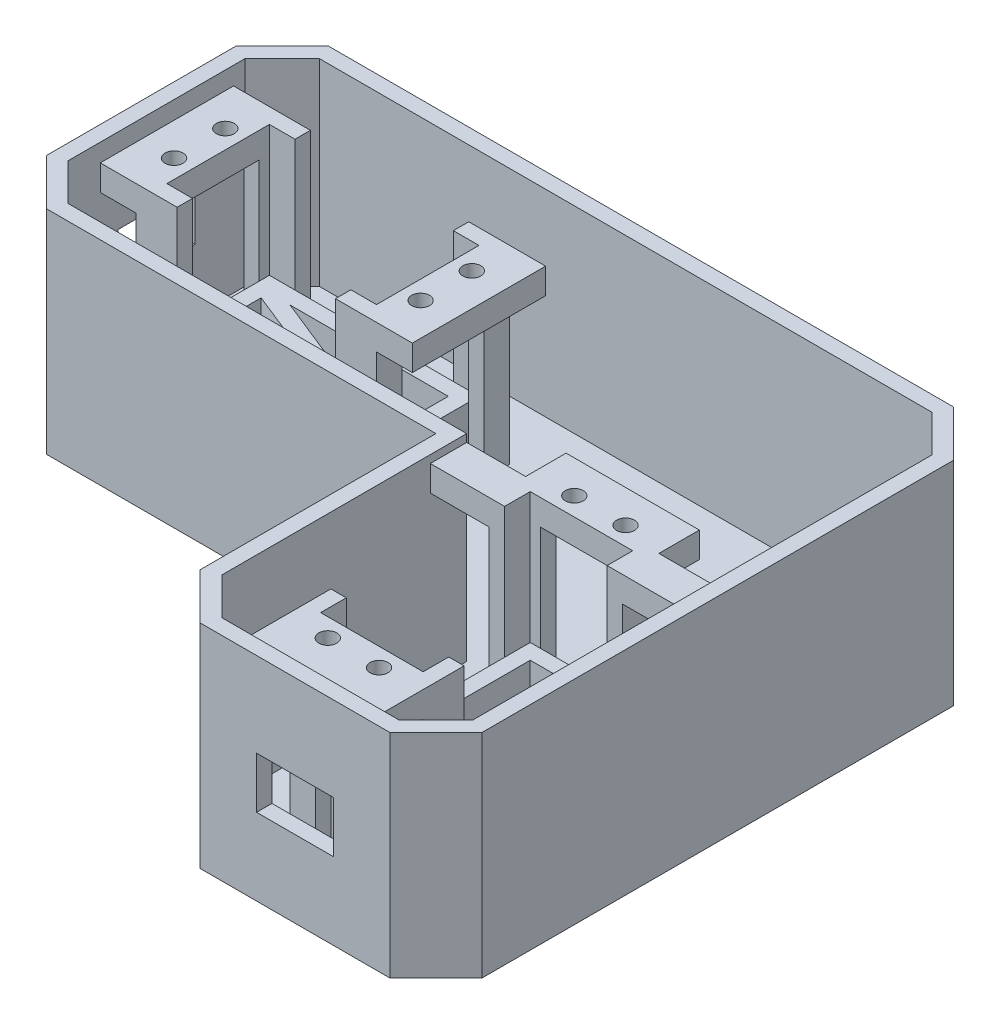
SolidWorks part; units mm, degrees
ref_plane "Front Plane" through (0, 0, 0) normal (0, 0, 1) x (1, 0, 0)
ref_plane "Top Plane" through (0, 0, 0) normal (0, 1, 0) x (1, 0, 0)
ref_plane "Right Plane" through (0, 0, 0) normal (1, 0, 0) x (0, 0, -1)
sketch "Sketch2" plane through (0, 0, 0) normal (0, 1, 0) x (1, 0, 0)
  line L0 (0, 46) -> (9, 55)
  line L1 (9, 0) -> (140, 0)
  line L2 (0, 9) -> (0, 46)
  line L3 (9, 55) -> (131, 55)
  line L4 (140, 0) -> (140, 46)
  line L5 (140, 0) -> (85, 0)
  line L6 (140, 0) -> (140, -46)
  line L7 (131, -55) -> (94, -55)
  line L8 (85, 0) -> (85, -46)
  line L9 (0, 9) -> (9, 0)
  line L10 (94, -55) -> (85, -46)
  line L11 (140, -46) -> (131, -55)
  line L12 (131, 55) -> (140, 46)
  point P0 (0, 0)
  point P1 (140, 55)
  point P2 (0, 55)
  point P5 (85, -55)
  point P6 (140, -55)
  dimension "D1" = 55
  dimension "D2" = 140
  dimension "D3" = 55
  dimension "D4" = 55
extrude "Boss-Extrude1" add sketch "Sketch2" along normal blind 55 contours L12 L3 L0 L2 L9 L1 L4 | L6 L11 L7 L10 L8 L5
shell "Shell1" thickness 3
ref_plane "Plane1" through (0, 41.5, 0) normal (0, 1, 0) x (1, 0, 0)
sketch "Sketch4" plane through (0, 0, 0) normal (0, 0, 1) x (1, 0, 0)
  line L0 (60.5, 41.5) -> (-60.5, 41.5) construction
  line L1 (-7.3258, 41.5) -> (147.3258, 41.5)
  line L2 (-7.3258, 41.5) -> (-7.3258, 64.0976)
  line L3 (-7.3258, 64.0976) -> (147.3258, 64.0976)
  line L4 (147.3258, 41.5) -> (147.3258, 64.0976)
  line L6 (-7.3258, 41.5) -> (147.3258, 41.5)
  line L7 (-7.3258, 41.5) -> (-7.3258, -2.7209)
  line L8 (-7.3258, -2.7209) -> (147.3258, -2.7209)
  line L9 (147.3258, 41.5) -> (147.3258, -2.7209)
extrude "Cut-Extrude1" cut sketch "Sketch4" against normal through all both and the other way through all contours L2 L1 L4 L3
sketch "Sketch5" plane through (0, 41.5, 0) normal (0, 1, 0) x (1, 0, 0)
  line L0 (112.5, -55) -> (112.5, -30) construction
  line L1 (94, -55) -> (131, -55) construction
  line L2 (112.5, -30) -> (112.5, -40) construction
  line L4 (102.5, 0.9) -> (122.5, 0.9)
  line L5 (102.5, 0.9) -> (102.5, -40)
  line L6 (102.5, -40) -> (122.5, -40)
  line L7 (122.5, 0.9) -> (122.5, -40)
  circle A0 centre (112.5, -30) radius 2.5
  point P9 (112.5, -40)
  dimension "D5" = 5
  dimension "D1" = 25
  dimension "D2" = 10
  dimension "D3" = 40.9
  dimension "D4" = 20
sketch "Sketch6" plane through (0, 0, 0) normal (0, -1, 0) x (1, 0, 0)
  line L0 (112.5, 55) -> (112.5, 30) construction
  circle A0 centre (112.5, 30) radius 3.8
  dimension "D1" = 7.6
extrude "Boss-Extrude2" add sketch "Sketch6" along normal blind 6
sketch "Sketch8" plane through (0, 3, 0) normal (0, 1, 0) x (1, 0, 0)
  line L0 (99.5, -35) -> (99.5, -43)
  line L1 (104.5, -43) -> (99.5, -43)
  line L4 (99.5, -4.1) -> (125.5, -4.1)
  line L5 (122.5, 0.9) -> (102.5, 0.9)
  line L6 (102.5, 0.9) -> (102.5, -40)
  line L7 (102.5, -40) -> (122.5, -40)
  line L8 (125.5, 3.9) -> (99.5, 3.9)
  line L9 (99.5, 3.9) -> (99.5, -43)
  line L10 (125.5, -43) -> (125.5, 3.9)
  line L11 (99.5, -43) -> (125.5, -43)
  line L12 (125.5, 3.9) -> (99.5, 3.9)
  line L13 (99.5, 3.9) -> (99.5, -43)
  line L14 (125.5, -43) -> (125.5, 3.9)
  line L15 (99.5, -43) -> (125.5, -43)
  line L16 (122.5, -40) -> (122.5, 0.9)
  line L17 (125.5, -4.1) -> (125.5, -35)
  line L18 (125.5, -35) -> (99.5, -35)
  line L19 (104.5, 3.9) -> (104.5, -43)
  line L20 (104.5, -43) -> (120.5, -43)
  line L21 (120.5, -43) -> (120.5, 3.9)
  line L22 (99.5, -4.1) -> (102.5, -4.1)
  line L23 (102.5, -4.1) -> (102.5, 0.9)
  line L24 (102.5, 0.9) -> (104.5, 0.9)
  line L25 (104.5, 0.9) -> (104.5, 3.9)
  line L26 (120.5, 3.9) -> (120.5, 0.9)
  line L27 (120.5, 0.9) -> (122.5, 0.9)
  line L28 (122.5, -4.1) -> (122.5, 0.9)
  line L29 (122.5, -4.1) -> (125.5, -4.1)
  line L30 (125.5, -35) -> (122.5, -35)
  line L31 (122.5, -35) -> (122.5, -40)
  line L32 (122.5, -40) -> (120.5, -40)
  line L33 (120.5, -40) -> (120.5, -43)
  line L34 (120.5, -43) -> (125.5, -43)
  line L35 (104.5, -43) -> (104.5, -40)
  line L36 (104.5, -40) -> (102.5, -40)
  line L37 (102.5, -40) -> (102.5, -35)
  line L38 (102.5, -35) -> (99.5, -35)
  dimension "D5" = 5
  dimension "D2" = 8
  dimension "D4" = 8
  dimension "D6" = 5
extrude "Boss-Extrude3" add sketch "Sketch8" along normal blind 37 contours L7 L6 L28 L23 L24 L25 | L21 L15 L14 L18 L16 L7 | L16 L14 L12 L5 | L19 L12 L13 L4 L6 L5 region at (101.5, 3, 39.5) region at (101.5, 3, -0.4) region at (123.5, 3, 39.5) region at (123.5, 3, -0.4)
sketch "Sketch9" plane through (0, 40, 0) normal (0, 1, 0) x (1, 0, 0)
  line L3 (99.5, 10.9) -> (125.5, 10.9)
  line L7 (99.5, -50) -> (125.5, -50)
  line L8 (125.5, -43) -> (125.5, -35) construction
  line L11 (99.5, -40) -> (125.5, -40)
  line L13 (99.5, 3.9) -> (99.5, -4.1) construction
  line L16 (125.5, 0.9) -> (99.5, 0.9)
  line L18 (99.5, -40) -> (99.5, -50)
  line L19 (125.5, -50) -> (125.5, -40)
  line L20 (125.5, 0.9) -> (125.5, 10.9)
  line L21 (99.5, 10.9) -> (99.5, 0.9)
  line L22 (99.5, -50) -> (125.5, -40) construction
  line L23 (99.5, 0.9) -> (125.5, 10.9) construction
  dimension "D2" = 10
  dimension "D1" = 10
  dimension "D3" = 26
  dimension "D4" = 26
  dimension "D5" = 40.9
extrude "Boss-Extrude4" add sketch "Sketch9" against normal blind 5
sketch "Sketch10" plane through (0, 40, 0) normal (0, 1, 0) x (1, 0, 0)
  line L0 (112.5, 10.9) -> (112.5, -50) construction
  line L1 (125.5, 10.9) -> (99.5, 10.9) construction
  line L2 (99.5, -50) -> (125.5, -50) construction
  line L3 (107.5, 4.5) -> (117.5, 4.5)
  line L4 (102.5, -19.55) -> (122.5, -19.55) construction
  line L5 (102.5, 0.9) -> (102.5, -40) construction
  line L6 (122.5, 0.9) -> (122.5, -40) construction
  line L7 (102.5, 0.9) -> (122.5, 0.9) construction
  circle A0 centre (107.5, 4.5) radius 1.75
  circle A1 centre (117.5, 4.5) radius 1.75
  circle A2 centre (117.5, -43.6) radius 1.75
  circle A3 centre (107.5, -43.6) radius 1.75
  point P9 (112.5, 4.5)
  dimension "D2" = 10
  dimension "D1" = 3.5
  dimension "D3" = 3.6
extrude "Cut-Extrude3" cut sketch "Sketch10" against normal up to next contours A0 | A1 | A2 | A3 region at (117.5, 40, -6.2005) region at (105.7995, 40, -4.5)
sketch "Sketch11" plane through (0, 40, 0) normal (0, 1, 0) x (1, 0, 0)
  line L0 (129.7574, -52) -> (95.2426, -52) construction
  line L1 (125.5, -52) -> (99.5, -52)
  line L2 (125.5, -52) -> (125.5, -50)
  line L3 (125.5, -50) -> (99.5, -50)
  line L4 (99.5, -52) -> (99.5, -50)
  line L5 (137, -44.7574) -> (137, 44.7574) construction
  line L6 (88, 3) -> (99.5, 3)
  line L7 (88, 3) -> (88, -4.1)
  line L8 (88, -4.1) -> (99.5, -4.1)
  line L9 (99.5, 3) -> (99.5, -4.1)
  line L10 (125.5, -4.1) -> (137, -4.1)
  line L11 (125.5, -4.1) -> (125.5, 3)
  line L12 (125.5, 3) -> (137, 3)
  line L13 (137, -4.1) -> (137, 3)
  dimension "D1" = 26
extrude "Boss-Extrude5" add sketch "Sketch11" against normal blind 5
sketch "Sketch12" plane through (0, 0, 55) normal (0, 0, 1) x (1, 0, 0)
  line L0 (112.5, 0) -> (112.5, 15) construction
  line L1 (131, 0) -> (94, 0) construction
  line L3 (105, 25) -> (120, 25)
  line L4 (105, 25) -> (105, 15)
  line L5 (105, 15) -> (120, 15)
  line L6 (120, 25) -> (120, 15)
  point P8 (112.5, 15)
  dimension "D2" = 10
  dimension "D1" = 15
  dimension "D3" = 15
extrude "Cut-Extrude4" cut sketch "Sketch12" against normal up to next
sketch "Sketch13" plane through (0, 3, 0) normal (0, 1, 0) x (1, 0, 0)
  line L1 (102.5, 0.9) -> (122.5, 0.9)
  line L2 (102.5, 0.9) -> (102.5, -40)
  line L3 (102.5, -40) -> (122.5, -40)
  line L4 (122.5, 0.9) -> (122.5, -40)
extrude "Boss-Extrude6" add sketch "Sketch13" along normal blind 11.5
sketch "Sketch14" plane through (0, 14.5, 0) normal (0, 1, 0) x (1, 0, 0)
  line L0 (112.5, 0.9) -> (112.5, -40) construction
  line L1 (102.5, 0.9) -> (122.5, 0.9) construction
  line L26 (105.5, -2.1) -> (105.5, -4.1)
  line L27 (105.5, -4.1) -> (105.5, -35)
  line L28 (105.5, -35) -> (105.5, -37)
  line L29 (105.5, -37) -> (119.5, -37)
  line L30 (119.5, -37) -> (119.5, -35)
  line L31 (119.5, -35) -> (119.5, -4.1)
  line L32 (119.5, -4.1) -> (119.5, -2.1)
  line L33 (119.5, -2.1) -> (105.5, -2.1)
  line L34 (105.5, -2.1) -> (105.5, -4.1)
  line L35 (105.5, -4.1) -> (105.5, -35)
  line L36 (105.5, -35) -> (105.5, -37)
  line L37 (105.5, -37) -> (119.5, -37)
  line L38 (119.5, -37) -> (119.5, -35)
  line L39 (119.5, -35) -> (119.5, -4.1)
  line L40 (119.5, -4.1) -> (119.5, -2.1)
  line L41 (119.5, -2.1) -> (105.5, -2.1)
  dimension "D1" = 3
extrude "Cut-Extrude5" cut sketch "Sketch14" against normal up to surface (11.5 mm away) up to face at (75.5675, 3, -1.4766)
sketch "Sketch15" plane through (0, 3, 0) normal (0, 1, 0) x (1, 0, 0)
  line L0 (119.5, -2.1) -> (105.5, -37) construction
  line L1 (105.5, -32.9711) -> (117.8838, -2.1)
  line L2 (111.1078, -18.9915) -> (113.8922, -20.1085)
  line L3 (107.1162, -37) -> (119.5, -6.1289)
  line L5 (105.5, -2.1) -> (119.5, -2.1)
  line L6 (105.5, -2.1) -> (105.5, -37)
  line L7 (105.5, -37) -> (119.5, -37)
  line L8 (119.5, -2.1) -> (119.5, -37)
  point P11 (112.5, -19.55)
  point P12 (111.1078, -18.9915)
  point P15 (113.8922, -20.1085)
  line M6 (119.5, -2.1) -> (105.5, -2.1)
  line M7 (105.5, -2.1) -> (105.5, -37)
  line M8 (105.5, -37) -> (119.5, -37)
  line M9 (119.5, -37) -> (119.5, -2.1)
extrude "Boss-Extrude7" add sketch "Sketch15" along normal blind 11.5 contours L0 L1 L2 M6 | L0 L2 L3 M9 | L0 L2 L1 M7 | L2 L0 L3 M8 region at (116.3352, 3, 11.9296) region at (115.252, 3, 10.6861) region at (109.748, 3, 28.4139) region at (108.6648, 3, 27.1704)
sketch "Sketch16" plane through (0, 0, 0) normal (-1, 0, 0) x (0, 0, 1)
  line L0 (-27.5, 0) -> (-27.5, 15) construction
  line L1 (-35, 25) -> (-20, 25)
  line L2 (-35, 25) -> (-35, 15)
  line L3 (-35, 15) -> (-20, 15)
  line L4 (-20, 25) -> (-20, 15)
  line L5 (-9, 0) -> (-46, 0) construction
  point P6 (-27.5, 15)
  point P9 (-27.5, 0)
  dimension "D1" = 15
  dimension "D2" = 10
  dimension "D3" = 15
extrude "Cut-Extrude6" cut sketch "Sketch16" against normal up to next
sketch "Sketch17" plane through (0, 41.5, 0) normal (0, 1, 0) x (1, 0, 0)
  line L0 (0, 27.5) -> (25, 27.5) construction
  line L1 (25, 27.5) -> (15, 27.5) construction
  line L2 (55.9, 37.5) -> (55.9, 17.5)
  line L3 (55.9, 37.5) -> (15, 37.5)
  line L4 (15, 37.5) -> (15, 17.5)
  line L5 (55.9, 17.5) -> (15, 17.5)
  line L6 (0, 46) -> (0, 9) construction
  line L8 (15, 37.5) -> (55.9, 37.5)
  line L9 (15, 37.5) -> (15, 17.5)
  line L10 (15, 17.5) -> (55.9, 17.5)
  line L11 (55.9, 37.5) -> (55.9, 17.5)
  circle A0 centre (25, 27.5) radius 2.5
  point P7 (15, 27.5)
  point P11 (0, 27.5)
  dimension "D1" = 25
  dimension "D2" = 5
  dimension "D3" = 20
  dimension "D4" = 40.9
  dimension "D5" = 10
  dimension "D6" = 30.9
sketch "Sketch18" plane through (0, 3, 0) normal (0, 1, 0) x (1, 0, 0)
  line L4 (55.9, 17.5) -> (55.9, 37.5)
  line L5 (55.9, 37.5) -> (15, 37.5)
  line L6 (15, 37.5) -> (15, 17.5)
  line L7 (15, 17.5) -> (55.9, 17.5)
  line L8 (58.9, 14.5) -> (58.9, 40.5)
  line L9 (12, 14.5) -> (58.9, 14.5)
  line L10 (12, 40.5) -> (12, 14.5)
  line L11 (58.9, 40.5) -> (12, 40.5)
  line L12 (58.9, 14.5) -> (58.9, 40.5)
  line L13 (12, 14.5) -> (58.9, 14.5)
  line L14 (12, 40.5) -> (12, 14.5)
  line L15 (58.9, 40.5) -> (12, 40.5)
  line L16 (12, 35.5) -> (58.9, 35.5)
  line L17 (58.9, 19.5) -> (12, 19.5)
  line L18 (20, 40.5) -> (20, 14.5)
  line L20 (50.9, 40.5) -> (50.9, 14.5)
  dimension "D5" = 8
  dimension "D6" = 8
extrude "Boss-Extrude8" add sketch "Sketch18" along normal blind 37 contours L18 L15 L14 L16 L6 L5 | L15 L20 L5 L4 L16 L12 | L7 L20 L13 L12 L17 L4 | L18 L7 L6 L17 L14 L13 region at (55.4, 3, -16.5) region at (55.4, 3, -38.5) region at (15.5, 3, -16.5) region at (15.5, 3, -38.5)
sketch "Sketch19" plane through (0, 40, 0) normal (0, 1, 0) x (1, 0, 0)
  line L0 (20, 40.5) -> (12, 40.5) construction
  line L1 (15, 40.5) -> (5, 40.5)
  line L2 (15, 40.5) -> (15, 14.5)
  line L3 (15, 14.5) -> (5, 14.5)
  line L4 (5, 40.5) -> (5, 14.5)
  line L5 (35.45, 37.5) -> (35.45, 17.5) construction
  line L6 (55.9, 37.5) -> (15, 37.5) construction
  line L7 (55.9, 17.5) -> (15, 17.5) construction
  line L8 (15, 27.5) -> (5, 27.5) construction
  line L9 (11.4, 22.5) -> (11.4, 32.5)
  line L10 (3, 10.2426) -> (3, 44.7574) construction
  line L11 (15, 40.5) -> (5, 40.5)
  line L12 (15, 14.5) -> (5, 14.5)
  line L13 (15, 40.5) -> (5, 40.5)
  line L14 (15, 14.5) -> (5, 14.5)
  line L15 (15, 40.5) -> (5, 40.5)
  line L16 (15, 14.5) -> (5, 14.5)
  line L17 (15, 40.5) -> (5, 40.5)
  line L18 (15, 14.5) -> (5, 14.5)
  line L19 (15, 40.5) -> (5, 40.5)
  line L20 (15, 14.5) -> (5, 14.5)
  line L21 (15, 40.5) -> (5, 40.5)
  line L22 (15, 14.5) -> (5, 14.5)
  line L23 (15, 40.5) -> (5, 40.5)
  line L24 (15, 14.5) -> (5, 14.5)
  line L25 (55.9, 27.5) -> (65.9, 27.5) construction
  line L26 (55.9, 14.5) -> (65.9, 14.5)
  line L27 (55.9, 40.5) -> (65.9, 40.5)
  line L28 (55.9, 14.5) -> (65.9, 14.5)
  line L29 (55.9, 40.5) -> (65.9, 40.5)
  line L30 (55.9, 14.5) -> (65.9, 14.5)
  line L31 (55.9, 40.5) -> (65.9, 40.5)
  line L32 (55.9, 14.5) -> (65.9, 14.5)
  line L33 (55.9, 40.5) -> (65.9, 40.5)
  line L34 (55.9, 14.5) -> (65.9, 14.5)
  line L35 (55.9, 40.5) -> (65.9, 40.5)
  line L36 (55.9, 14.5) -> (65.9, 14.5)
  line L37 (55.9, 40.5) -> (65.9, 40.5)
  line L38 (55.9, 14.5) -> (65.9, 14.5)
  line L39 (55.9, 40.5) -> (65.9, 40.5)
  line L40 (59.5, 22.5) -> (59.5, 32.5)
  line L41 (65.9, 40.5) -> (65.9, 14.5)
  line L42 (55.9, 14.5) -> (65.9, 14.5)
  line L43 (55.9, 40.5) -> (55.9, 14.5)
  line L44 (55.9, 40.5) -> (65.9, 40.5)
  circle A0 centre (11.4, 32.5) radius 1.75
  circle A1 centre (11.4, 22.5) radius 1.75
  circle A2 centre (11.4, 32.5) radius 1.75
  circle A3 centre (11.4, 22.5) radius 1.75
  circle A4 centre (11.4, 32.5) radius 1.75
  circle A5 centre (11.4, 22.5) radius 1.75
  circle A6 centre (11.4, 32.5) radius 1.75
  circle A7 centre (11.4, 22.5) radius 1.75
  circle A8 centre (11.4, 32.5) radius 1.75
  circle A9 centre (11.4, 22.5) radius 1.75
  circle A10 centre (11.4, 32.5) radius 1.75
  circle A11 centre (11.4, 22.5) radius 1.75
  circle A12 centre (11.4, 32.5) radius 1.75
  circle A13 centre (11.4, 22.5) radius 1.75
  circle A14 centre (11.4, 32.5) radius 1.75
  circle A15 centre (11.4, 22.5) radius 1.75
  circle A16 centre (59.5, 22.5) radius 1.75
  circle A17 centre (59.5, 32.5) radius 1.75
  circle A18 centre (59.5, 22.5) radius 1.75
  circle A19 centre (59.5, 32.5) radius 1.75
  circle A20 centre (59.5, 22.5) radius 1.75
  circle A21 centre (59.5, 32.5) radius 1.75
  circle A22 centre (59.5, 22.5) radius 1.75
  circle A23 centre (59.5, 32.5) radius 1.75
  circle A24 centre (59.5, 22.5) radius 1.75
  circle A25 centre (59.5, 32.5) radius 1.75
  circle A26 centre (59.5, 22.5) radius 1.75
  circle A27 centre (59.5, 32.5) radius 1.75
  circle A28 centre (59.5, 22.5) radius 1.75
  circle A29 centre (59.5, 32.5) radius 1.75
  circle A30 centre (59.5, 22.5) radius 1.75
  circle A31 centre (59.5, 32.5) radius 1.75
  point P19 (11.4, 27.5)
  point P20 (0, 0)
  point P25 (-31.8865, 36.4769)
  point P62 (59.5, 27.5)
  line M12 (20, 40.5) -> (12, 40.5)
  line M13 (12, 40.5) -> (12, 35.5)
  line M14 (12, 35.5) -> (15, 35.5)
  line M15 (15, 35.5) -> (15, 37.5)
  dimension "D1" = 10
  dimension "D4" = 3.5
  dimension "D2" = 26
  dimension "D3" = 10
  dimension "D6" = 3.6
extrude "Boss-Extrude9" add sketch "Sketch19" against normal blind 5 contours L1 L4 L3 L2 A1 A0 M14 M13 | L2 M12 M13 M14 M15 | L27 L43 L26 L41 A17 A16 region at (13.5, 40, -38) region at (9.6481, 40, -26.8023) region at (61.0119, 40, -27.5)
sketch "Sketch20" plane through (0, 3, 0) normal (0, 1, 0) x (1, 0, 0)
  line L1 (15, 37.5) -> (55.9, 37.5)
  line L2 (15, 37.5) -> (15, 17.5)
  line L3 (15, 17.5) -> (55.9, 17.5)
  line L4 (55.9, 37.5) -> (55.9, 17.5)
extrude "Boss-Extrude10" add sketch "Sketch20" along normal blind 11.5
sketch "Sketch21" plane through (0, 14.5, 0) normal (0, 1, 0) x (1, 0, 0)
  line L0 (18, 20.5) -> (18, 34.5)
  line L1 (15, 17.5) -> (55.9, 17.5)
  line L2 (15, 17.5) -> (15, 37.5)
  line L3 (15, 37.5) -> (55.9, 37.5)
  line L4 (55.9, 17.5) -> (55.9, 37.5)
  line L5 (18, 34.5) -> (52.9, 34.5)
  line L6 (52.9, 20.5) -> (52.9, 34.5)
  line L7 (18, 20.5) -> (52.9, 20.5)
  line L8 (52.9, 20.5) -> (18, 34.5) construction
  line L9 (36.0085, 28.8922) -> (34.8915, 26.1078)
  line L10 (48.8711, 20.5) -> (18, 32.8838)
  line L11 (52.9, 22.1162) -> (22.0289, 34.5)
  point P13 (35.45, 27.5)
  point P16 (34.8915, 26.1078)
  point P19 (36.0085, 28.8922)
  dimension "D3" = 30.8711
  dimension "D4" = 30.8711
extrude "Cut-Extrude7" cut sketch "Sketch21" against normal up to surface (11.5 mm away) contours L7 L10 L0 | L11 L6 L5 region at (28.2904, 14.5, -24.6279) region at (42.6096, 14.5, -30.3721) up to face at (75.5675, 3, -1.4766)
equation "\"width of arm\"=55"
equation "\"D1@Sketch2\"=\"width of arm\""
equation "\"height of arm\"= 140"
equation "\"D2@Sketch2\"=\"height of arm\""
equation "\"width connection rotatation\"=55"
equation "\"D3@Sketch2\"=\"width connection rotatation\""
equation "\"length connection rotator\"=55"
equation "\"D4@Sketch2\"=\"length connection rotator\""
equation "\"length from outer edge to servo centre\"=25"
equation "\"D1@Sketch5\"=\"length from outer edge to servo centre\""
equation "\"D2@Sketch5\"=10"
equation "\"D3@Sketch5\"=40.9"
equation "\"D4@Sketch5\"=20"
equation "\"D5@Sketch5\"=5"
equation "\"pin diam\"=7.6"
equation "\"D1@Sketch6\"=\"pin diam\""
equation "\"D2@Sketch8\"=8"
equation "\"D4@Sketch8\"=8"
equation "\"D5@Sketch8\"=\"wall mount dist\""
equation "\"wall mount dist\"=5"
equation "\"D6@Sketch8\"=\"wall mount dist\""
equation "\"D1@Sketch9\"=10"
equation "\"D2@Sketch9\"=10"
equation "\"D3@Sketch9\"=26"
equation "\"D4@Sketch9\"=26"
equation "\"D5@Sketch9\"=40.90"
equation "\"hole size\"=3.5"
equation "\"D1@Sketch10\"=\"hole size\""
equation "\"D2@Sketch10\"=10"
equation "\"D3@Sketch10\"=3.6"
equation "\"D1@Sketch11\"=26"
equation "\"D1@Sketch12\"=15"
equation "\"D2@Sketch12\"=10"
equation "\"D3@Sketch12\"=15"
equation "\"D1@Sketch15\"=3"
equation "\"D1@Sketch17\"=25"
equation "\"D3@Sketch18\"=\"wall mount dist\""
equation "\"D4@Sketch18\"=\"wall mount dist\""
equation "\"D5@Sketch18\"=8"
equation "\"D6@Sketch18\"=8"
equation "\"D1@Sketch19\"=10"
equation "\"D2@Sketch19\"=26"
equation "\"D3@Sketch19\"=10"
equation "\"D4@Sketch19\"=\"hole size\""
equation "\"D5@Sketch19\"=2"
equation "\"D6@Sketch19\"=3.6"
equation "\"D2@Sketch21\"=3"
